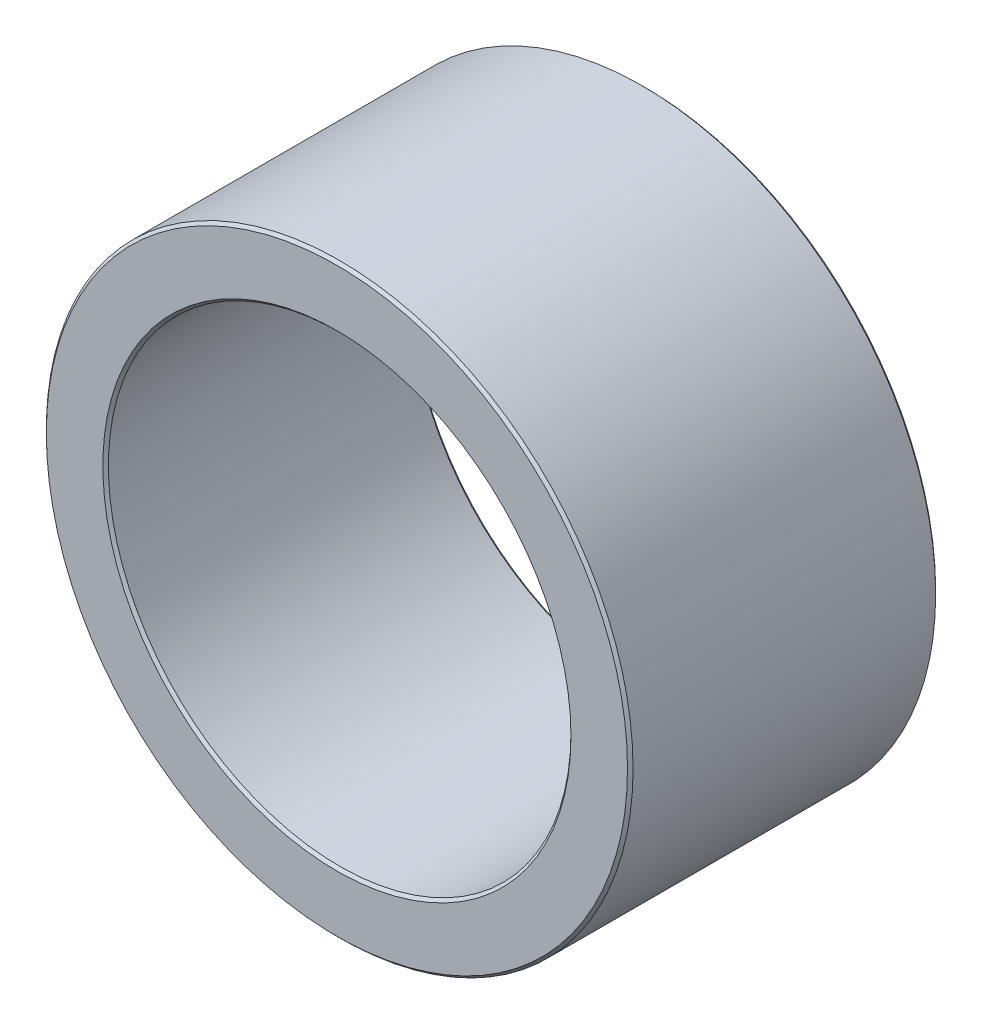
SolidWorks part; units mm, degrees
ref_plane "Front Plane" through (0, 0, 0) normal (0, 0, 1) x (1, 0, 0)
ref_plane "Top Plane" through (0, 0, 0) normal (0, 1, 0) x (1, 0, 0)
ref_plane "Right Plane" through (0, 0, 0) normal (1, 0, 0) x (0, 0, -1)
sketch "Sketch1" plane through (0, 0, 0) normal (0, 0, 1) x (1, 0, 0)
  circle A0 centre (0, 0) radius 9.52
  circle A1 centre (0, 0) radius 7.505
  point P8 (0, -9.52)
  point P9 (0, 9.52)
  dimension "ID" = 15.01
  dimension "OD" = 19.04
sketch "Sketch2" plane through (0, 0, 0) normal (1, 0, 0) x (0, 0, -1)
  line L0 (5, 0) -> (-5, 0) construction
  line L1 (5, 9.52) -> (-5, 9.52) construction
  point P4 (0, 0)
  point P8 (0, 9.52)
  point P9 (0, 9.52)
  dimension "Length" = 10
sketch "Sketch5" plane through (0, 0, 0) normal (0, 0, 1) x (1, 0, 0)
  circle A0 centre (0, 0) radius 7.505 construction
  circle A1 centre (0, 0) radius 9.52 construction
  circle A2 centre (0, 0) radius 7.505
  circle A3 centre (0, 0) radius 9.52
extrude "Boss-Extrude1" add sketch "Sketch5" along normal up to vertex and the other way up to vertex up to point (0, 0, 5) other way up to point (0, 0, -5)
chamfer "Chamfer1" distance 0.0901 angle 45 4 edges at (9.52, 0, -5) (7.505, 0, -5) (7.505, 0, 5) (9.52, 0, 5)
equation "\"D1@Chamfer1\"=\"ID@Sketch1\"*.006"
